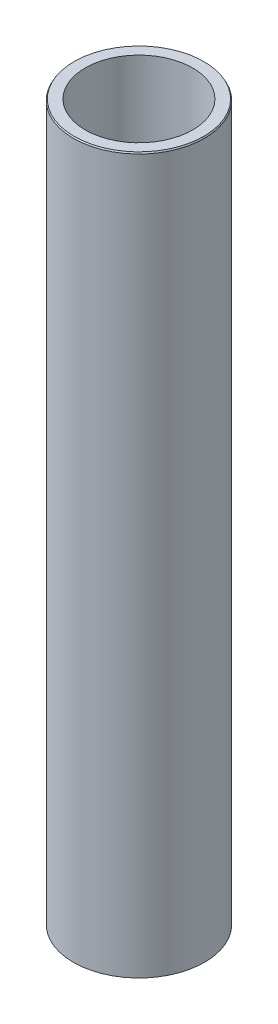
SolidWorks part; units mm, degrees
ref_plane "Front Plane" through (0, 0, 0) normal (0, 0, 1) x (1, 0, 0)
ref_plane "Top Plane" through (0, 0, 0) normal (0, 1, 0) x (1, 0, 0)
ref_plane "Right Plane" through (0, 0, 0) normal (1, 0, 0) x (0, 0, -1)
sketch "Sketch1" plane through (0, 0, 0) normal (0, 1, 0) x (1, 0, 0)
  circle A0 centre (0, 0) radius 55
  dimension "SHAFT_OD" = 110
extrude "Boss-Extrude1" add sketch "Sketch1" along normal blind 600
sketch "Sketch2" plane through (0, 0, 0) normal (0, 1, 0) x (1, 0, 0)
  circle A0 centre (0, 0) radius 45.05
  dimension "BORE_D" = 90.0999
extrude "Cut-Extrude1" cut sketch "Sketch2" along normal through all
chamfer "Chamfer1" distance 1.1225 angle 30 2 edges at (0, 600, 55) (0, 0, 55) first distance on face at (0, 600, 55) first distance on face at (0, 0, 45.05)
